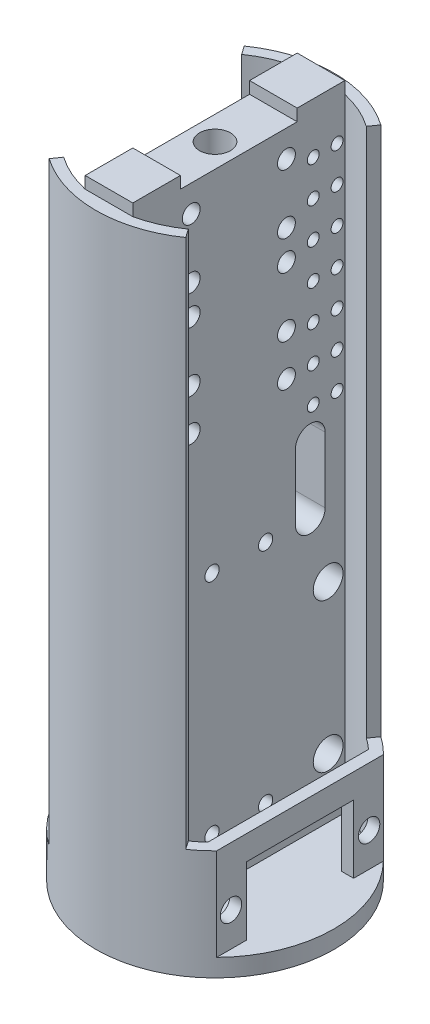
SolidWorks part; units mm, degrees
material "ABS"
ref_plane "Front Plane" through (0, 0, 0) normal (0, 0, 1) x (1, 0, 0)
ref_plane "Top Plane" through (0, 0, 0) normal (0, 1, 0) x (1, 0, 0)
ref_plane "Right Plane" through (0, 0, 0) normal (1, 0, 0) x (0, 0, -1)
sketch "Sketch1" plane through (0, 0, 0) normal (0, 1, 0) x (1, 0, 0)
  line L0 (-5.08, 22.6139) -> (-5.08, -22.6139)
  line L1 (-5.08, -22.6139) -> (5.08, -22.6139) construction
  line L2 (5.08, -22.6139) -> (5.08, 22.6139)
  line L3 (0, 0) -> (0, -22.6139) construction
  line L4 (0, 0) -> (-12.7, 0) construction
  line L5 (-5.08, 19.05) -> (-12.7, 19.05)
  line L6 (-5.08, 19.05) -> (-5.08, -19.05)
  line L7 (-5.08, -19.05) -> (-12.7, -19.05)
  line L8 (-12.7, 19.05) -> (-12.7, -19.05)
  line L9 (-19.05, 13.202) -> (-19.05, -13.202)
  line L11 (18.1392, -17.78) -> (18.1392, 17.78)
  line L13 (15.5992, 17.1424) -> (15.5992, -17.1424)
  circle A0 centre (0, 0) radius 25.4 construction
  circle A1 centre (0, 0) radius 23.1775 construction
  circle A2 centre (0, 0) radius 3.302
  arc A3 (15.5992, -17.1424) -> (15.5992, 17.1424) centre (0, 0) cw
  arc A4 (18.1392, 17.78) -> (18.1392, -17.78) centre (0, 0) ccw
  arc A5 (18.1392, 17.78) -> (18.1392, -17.78) centre (0, 0) cw
  arc A6 (18.1392, 14.4279) -> (18.1392, -14.4279) centre (0, 0) cw
  dimension "D1" = 2.2225
  dimension "D2" = 50.8
  dimension "D3" = 6.604
  dimension "D8" = 35.56
  dimension "D9" = 2.54
  dimension "D4" = 10.16
  dimension "D5" = 7.62
  dimension "D6" = 38.1
  dimension "D7" = 6.35
extrude "bottom_plate" add sketch "Sketch1" against normal blind 3.81 contours L11 A6 A5 | A6 L11 | A4 L11 | A2 region at (18.5022, 0, 16.104) region at (20.1746, 0, 0)
extrude "lip" add sketch "Sketch1<4>" along normal blind 5.715 contours A0 A1 | L11 A4 A3 L13 | A3 L0 L2 A2 | A3 L9 L0 L7 L8 L5 region at (0, 0, -22.7029) region at (-14.6207, 0, 0) region at (-24.7309, 0, 0)
sketch "Sketch1<4>" plane through (0, 0, 0) normal (0, 1, 0) x (1, 0, 0) same geometry as "Sketch1"
sketch "Sketch2" plane through (0, 5.715, 0) normal (0, 1, 0) x (1, 0, 0)
  line L0 (5.08, 22.6139) -> (5.08, -22.6139)
  line L1 (5.08, -22.6139) -> (5.08, 22.6139) construction
  line L2 (0, 0) -> (14.5688, 20.8065) construction
  line L3 (13.2941, 18.9859) -> (14.5688, 20.8065)
  line L4 (0, 0) -> (14.5688, -20.8065) construction
  line L5 (14.5688, -20.8065) -> (13.2941, -18.9859)
  line L6 (-14.5688, 20.8065) -> (-13.2941, 18.9859)
  line L7 (0, 0) -> (-14.5688, 20.8065) construction
  line L8 (-5.08, 22.6139) -> (-5.08, -22.6139)
  line L9 (5.08, 22.6139) -> (-5.08, 22.6139) construction
  line L10 (-14.5688, -20.8065) -> (0, 0) construction
  line L11 (-13.2941, -18.9859) -> (-14.5688, -20.8065)
  line L12 (0, 25.4) -> (0, -25.4) construction
  line L13 (-5.08, -22.6139) -> (5.08, -22.6139) construction
  arc A1 (5.08, 22.6139) -> (13.2941, 18.9859) centre (0, 0) cw
  arc A2 (-14.5688, 20.8065) -> (14.5688, 20.8065) centre (0, 0) cw
  arc A4 (14.5688, -20.8065) -> (-14.5688, -20.8065) centre (0, 0) cw
  arc A5 (13.2941, -18.9859) -> (5.08, -22.6139) centre (0, 0) cw
  arc A7 (-5.08, 22.6139) -> (-13.2941, 18.9859) centre (0, 0) ccw
  arc A8 (-5.08, -22.6139) -> (-13.2941, -18.9859) centre (0, 0) cw
  circle A9 centre (0, 0) radius 3.302
  arc A10 (18.1392, 17.78) -> (18.1392, -17.78) centre (0, 0) ccw construction
  dimension "D1" = 35
  dimension "D5" = 2.2225
  dimension "D2" = 35
  dimension "D3" = 35
  dimension "D4" = 35
  dimension "D6" = 2.2225
extrude "Boss-Extrude1" add sketch "Sketch2" along normal blind 127
sketch "Sketch3" plane through (-5.08, 0, 0) normal (-1, 0, 0) x (0, 0, 1)
  line L0 (0, 0) -> (0, 132.715) construction
  line L1 (-22.6139, 132.715) -> (22.6139, 132.715) construction
  line L2 (-19.05, 44.45) -> (19.05, 44.45) construction
  line L4 (-19.05, 12.7) -> (19.05, 12.7) construction
  line L5 (-5.715, 58.42) -> (5.715, 58.42) construction
  line L6 (-5.715, 10.16) -> (5.715, 10.16) construction
  line L7 (-19.05, 44.45) -> (-19.05, 55.88) construction
  line L8 (15.24, 72.39) -> (15.24, 58.42) construction
  line L11 (18.415, 72.39) -> (18.415, 58.42)
  line L12 (12.065, 72.39) -> (12.065, 58.42)
  line L13 (15.24, 58.42) -> (5.715, 58.42) construction
  line L14 (-15.24, 72.39) -> (-15.24, 58.42) construction
  line L15 (-12.065, 72.39) -> (-12.065, 58.42)
  line L16 (-18.415, 72.39) -> (-18.415, 58.42)
  line L17 (-15.24, 58.42) -> (-5.715, 58.42) construction
  line L18 (10.16, 86.36) -> (-10.16, 86.36) construction
  line L19 (-10.16, 107.95) -> (-10.16, 95.25) construction
  line L20 (-10.16, 107.95) -> (10.16, 107.95) construction
  line L21 (10.16, 107.95) -> (10.16, 95.25) construction
  line L22 (10.16, 95.25) -> (-10.16, 95.25) construction
  line L23 (-10.16, 127) -> (10.16, 127) construction
  line L24 (-10.16, 127) -> (-10.16, 114.3) construction
  line L25 (10.16, 114.3) -> (-10.16, 114.3) construction
  line L26 (10.16, 127) -> (10.16, 114.3) construction
  line L27 (-15.875, 78.74) -> (-20.955, 78.74) construction
  line L28 (-18.415, 72.39) -> (-18.415, 78.74) construction
  line L29 (-15.875, 86.36) -> (-20.955, 86.36) construction
  line L30 (-15.875, 93.98) -> (-20.955, 93.98) construction
  line L31 (-15.875, 101.6) -> (-20.955, 101.6) construction
  line L32 (-15.875, 109.22) -> (-20.955, 109.22) construction
  line L33 (-15.875, 116.84) -> (-20.955, 116.84) construction
  line L34 (-15.875, 124.46) -> (-20.955, 124.46) construction
  line L37 (-19.05, 0) -> (19.05, 0) construction
  circle A0 centre (-19.05, 44.45) radius 3.175
  circle A1 centre (19.05, 44.45) radius 3.175
  circle A2 centre (-19.05, 12.7) radius 3.175
  circle A3 centre (19.05, 12.7) radius 3.175
  circle A4 centre (-5.715, 58.42) radius 1.524
  circle A5 centre (5.715, 58.42) radius 1.524
  circle A6 centre (-5.715, 10.16) radius 1.524
  circle A7 centre (5.715, 10.16) radius 1.524
  arc A11 (18.415, 72.39) -> (12.065, 72.39) centre (15.24, 72.39) ccw
  arc A12 (12.065, 58.42) -> (18.415, 58.42) centre (15.24, 58.42) ccw
  arc A13 (-12.065, 72.39) -> (-18.415, 72.39) centre (-15.24, 72.39) ccw
  arc A14 (-18.415, 58.42) -> (-12.065, 58.42) centre (-15.24, 58.42) ccw
  circle A15 centre (10.16, 86.36) radius 1.905
  circle A16 centre (-10.16, 86.36) radius 1.905
  circle A17 centre (-10.16, 107.95) radius 1.905
  circle A18 centre (-10.16, 95.25) radius 1.905
  circle A19 centre (10.16, 107.95) radius 1.905
  circle A20 centre (10.16, 95.25) radius 1.905
  circle A21 centre (-10.16, 127) radius 1.905
  circle A22 centre (-10.16, 114.3) radius 1.905
  circle A23 centre (10.16, 114.3) radius 1.905
  circle A24 centre (10.16, 127) radius 1.905
  circle A25 centre (-20.955, 78.74) radius 1.27
  circle A26 centre (-15.875, 78.74) radius 1.27
  circle A27 centre (-20.955, 86.36) radius 1.27
  circle A28 centre (-15.875, 86.36) radius 1.27
  circle A29 centre (-20.955, 93.98) radius 1.27
  circle A30 centre (-15.875, 93.98) radius 1.27
  circle A31 centre (-20.955, 101.6) radius 1.27
  circle A32 centre (-15.875, 101.6) radius 1.27
  circle A33 centre (-20.955, 109.22) radius 1.27
  circle A34 centre (-15.875, 109.22) radius 1.27
  circle A35 centre (-20.955, 116.84) radius 1.27
  circle A36 centre (-15.875, 116.84) radius 1.27
  circle A37 centre (-20.955, 124.46) radius 1.27
  circle A38 centre (-15.875, 124.46) radius 1.27
  circle A39 centre (20.955, 124.46) radius 1.27
  circle A40 centre (15.875, 124.46) radius 1.27
  circle A41 centre (15.875, 116.84) radius 1.27
  circle A42 centre (20.955, 116.84) radius 1.27
  circle A43 centre (20.955, 109.22) radius 1.27
  circle A44 centre (15.875, 109.22) radius 1.27
  circle A45 centre (15.875, 101.6) radius 1.27
  circle A46 centre (20.955, 101.6) radius 1.27
  circle A47 centre (20.955, 93.98) radius 1.27
  circle A48 centre (15.875, 93.98) radius 1.27
  circle A49 centre (20.955, 86.36) radius 1.27
  circle A50 centre (15.875, 86.36) radius 1.27
  circle A51 centre (20.955, 78.74) radius 1.27
  circle A52 centre (15.875, 78.74) radius 1.27
  point P9 (0, 44.45)
  point P17 (0, 12.7)
  point P21 (0, 58.42)
  point P26 (0, 10.16)
  point P31 (15.24, 65.405)
  point P37 (-15.24, 65.405)
  point P48 (0, 86.36)
  point P61 (0, 107.95)
  dimension "D1" = 6.35
  dimension "D2" = 6.35
  dimension "D5" = 6.35
  dimension "D6" = 6.35
  dimension "D9" = 3.048
  dimension "D10" = 3.048
  dimension "D12" = 3.048
  dimension "D13" = 3.048
  dimension "D17" = 6.35
  dimension "D24" = 20.32
  dimension "D25" = 3.81
  dimension "D26" = 3.81
  dimension "D28" = 3.81
  dimension "D29" = 3.81
  dimension "D32" = 3.81
  dimension "D33" = 3.81
  dimension "D36" = 2.54
  dimension "D37" = 2.54
  dimension "D4" = 38.1
  dimension "D7" = 38.1
  dimension "D8" = 12.7
  dimension "D11" = 11.43
  dimension "D14" = 10.16
  dimension "D15" = 48.26
  dimension "D16" = 44.45
  dimension "D18" = 11.43
  dimension "D19" = 13.97
  dimension "D20" = 6.35
  dimension "D21" = 15.24
  dimension "D22" = 13.97
  dimension "D23" = 15.24
  dimension "D27" = 27.94
  dimension "D30" = 12.7
  dimension "D31" = 20.32
  dimension "D34" = 8.89
  dimension "D38" = 5.08
  dimension "D39" = 6.35
  dimension "D40" = 6.35
  dimension "D42" = 7.62
  dimension "D43" = 11.43
  dimension "D35" = 2
  dimension "D41" = 7
extrude "mounting_holes" cut sketch "Sketch3" against normal up to surface (10.16 mm away) contours A0 | A5 | A1 | A2 | A3 | A7 | A6 | L12 A12 L11 A11 | A4 | A15 | A16 | L16 A14 L15 A13 | A22 | A21 | A24 | A23 | A19 | A17 | A18 | A20 | A25 | A26 | A28 | A27 | A30 | A29 | A32 | A31 | A38 | A37 | A35 | A36 | A34 | A33 | A49 | A50 | A52 | A51 | A47 | A48 | A45 | A46 | A43 | A44 | A42 | A41 | A40 | A39 region at (-5.08, 65.405, 15.24) region at (-5.08, 44.45, -19.05) region at (-5.08, 44.45, 19.05) region at (-5.08, 12.7, -19.05) region at (-5.08, 12.7, 19.05) region at (-5.08, 58.42, -5.715) region at (-5.08, 58.42, 5.715) region at (-5.08, 10.16, -5.715) region at (-5.08, 10.16, 5.715) region at (-5.08, 86.36, 10.16) region at (-5.08, 86.36, -10.16) up to face at (5.08, 66.3575, 0)
sketch "Sketch4" plane through (0, 132.715, 0) normal (0, 1, 0) x (1, 0, 0)
  line L0 (-5.08, 22.6139) -> (-5.08, -22.6139) construction
  line L1 (-5.08, 22.6139) -> (5.08, 22.6139)
  line L2 (-5.08, 22.6139) -> (-5.08, 12.4539)
  line L3 (-5.08, 12.4539) -> (5.08, 12.4539)
  line L4 (5.08, 22.6139) -> (5.08, 12.4539)
  line L5 (-5.08, -12.4539) -> (5.08, -12.4539)
  line L6 (-5.08, -12.4539) -> (-5.08, -22.6139)
  line L7 (-5.08, -22.6139) -> (5.08, -22.6139)
  line L8 (5.08, -12.4539) -> (5.08, -22.6139)
  line L9 (5.08, -22.6139) -> (5.08, 22.6139) construction
  line L10 (5.08, -22.6139) -> (5.08, 22.6139) construction
  dimension "D1" = 10.16
  dimension "D2" = 10.16
extrude "notches" add sketch "Sketch4" along normal blind 2.54
sketch "Sketch7" plane through (0, 5.715, 0) normal (0, 1, 0) x (1, 0, 0)
  line L4 (13.2941, -18.9859) -> (14.5688, -20.8065)
  line L5 (18.1392, -17.78) -> (18.1392, 17.78)
  line L6 (14.5688, 20.8065) -> (13.2941, 18.9859)
  line L7 (15.5992, 17.1424) -> (15.5992, -17.1424)
  line L8 (13.2941, -18.9859) -> (14.5688, -20.8065)
  line L9 (18.1392, -17.78) -> (18.1392, 17.78)
  line L10 (14.5688, 20.8065) -> (13.2941, 18.9859)
  line L11 (15.5992, 17.1424) -> (15.5992, -17.1424)
  arc A4 (14.5688, -20.8065) -> (18.1392, -17.78) centre (0, 0) ccw
  arc A5 (18.1392, 17.78) -> (14.5688, 20.8065) centre (0, 0) ccw
  arc A6 (15.5992, 17.1424) -> (13.2941, 18.9859) centre (0, 0) ccw
  arc A7 (13.2941, -18.9859) -> (15.5992, -17.1424) centre (0, 0) ccw
  arc A8 (14.5688, -20.8065) -> (18.1392, -17.78) centre (0, 0) ccw
  arc A9 (18.1392, 17.78) -> (14.5688, 20.8065) centre (0, 0) ccw
  arc A10 (15.5992, 17.1424) -> (13.2941, 18.9859) centre (0, 0) ccw
  arc A11 (13.2941, -18.9859) -> (15.5992, -17.1424) centre (0, 0) ccw
  dimension "D1" = 0
extrude "switch_face" add sketch "Sketch7" along normal blind 13.97
sketch "Sketch8" plane through (18.1392, 0, 0) normal (1, 0, 0) x (0, 0, -1)
  line L0 (17.78, 0) -> (-17.78, 0) construction
  line L1 (-11.43, 14.478) -> (11.43, 14.478)
  line L2 (-11.43, 14.478) -> (-11.43, 0)
  line L3 (-11.43, 0) -> (11.43, 0)
  line L4 (11.43, 14.478) -> (11.43, 0)
  line L5 (11.43, 7.239) -> (14.732, 7.239) construction
  line L6 (-11.43, 7.239) -> (-14.732, 7.239) construction
  line L7 (0, 0) -> (0, 2.032) construction
  circle A0 centre (14.732, 7.239) radius 2.286
  circle A1 centre (-14.732, 7.239) radius 2.286
  circle A2 centre (0, 2.032) radius 2.032
  point P6 (0, 0)
  point P10 (0, 0)
  line M5 (-17.78, 0) -> (17.78, 0)
  dimension "D3" = 4.572
  dimension "D5" = 4.572
  dimension "D7" = 4.064
  dimension "D1" = 14.478
  dimension "D2" = 22.86
  dimension "D4" = 3.302
  dimension "D6" = 3.302
extrude "switch_mount" cut sketch "Sketch8" against normal blind 6.35 contours A1 | A0 | A2 | L4 L1 L2 A2 M5 | A2 | L2 L1 L4 L3 region at (18.1392, 2.032, 0) region at (18.1392, 7.4514, 0) region at (18.1392, 7.239, -14.732) region at (18.1392, 7.239, 14.732)
extrude "indicator_cut" cut sketch "Sketch8<3>" against normal up to surface (20.2386 mm away) from surface contours A2 region at (18.1392, 2.032, 0) up to face at (5.7605, 51.7525, 0) starting at face at (-5.08, 78.74, -14.605)
sketch "Sketch8<3>" plane through (18.1392, 0, 0) normal (1, 0, 0) x (0, 0, -1) same geometry as "Sketch8"
